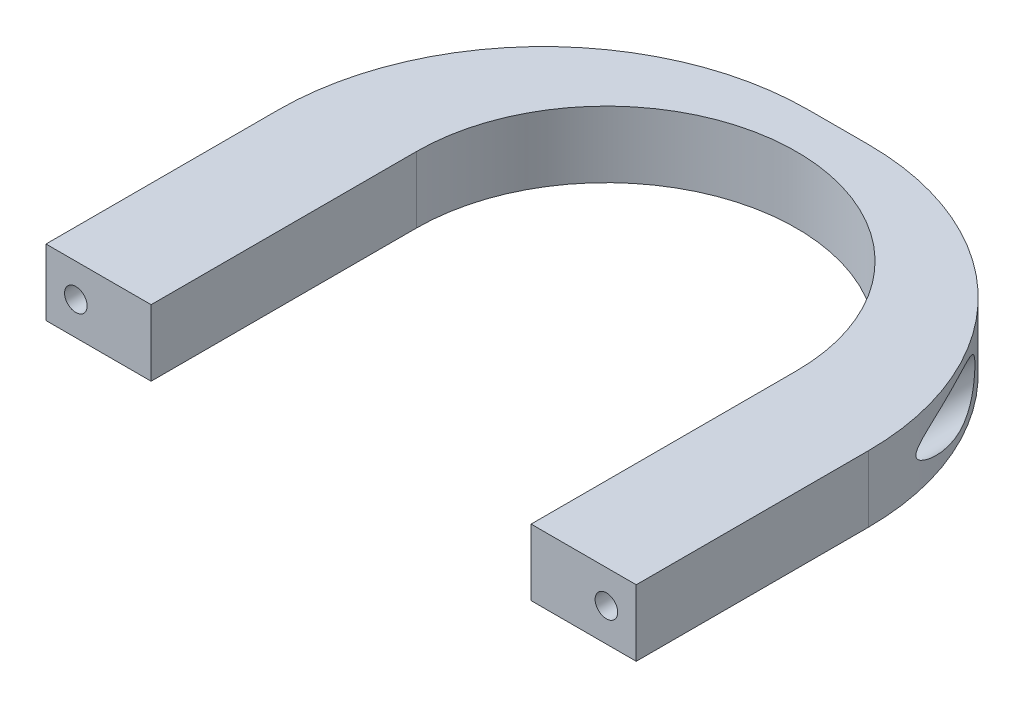
SolidWorks part; units mm, degrees
ref_plane "前视基准面" through (0, 0, 0) normal (0, 0, 1) x (1, 0, 0)
ref_plane "上视基准面" through (0, 0, 0) normal (0, 1, 0) x (1, 0, 0)
ref_plane "右视基准面" through (0, 0, 0) normal (1, 0, 0) x (0, 0, -1)
sketch "草图1" plane through (0, 0, 0) normal (0, 1, 0) x (1, 0, 0)
  line L0 (28.65, -40) -> (44.5, -40)
  line L1 (-44.5, 35) -> (44.5, 35)
  line L2 (-44.5, 35) -> (-44.5, -40)
  line L3 (-44.5, -40) -> (-28.65, -40)
  line L4 (44.5, 35) -> (44.5, -40)
  line L6 (-28.65, 0) -> (-28.65, -40)
  line L8 (28.65, 0) -> (28.65, -40)
  arc A0 (28.65, 0) -> (-28.65, 0) centre (0, 0) ccw
  dimension "D1" = 57.3
  dimension "D2" = 89
  dimension "D3" = 44.5
  dimension "D4" = 40
  dimension "D5" = 35
extrude "凸台-拉伸1" add sketch "草图1" along normal blind 10
sketch "草图2" plane through (0, 0, 40) normal (0, 0, 1) x (1, 0, 0)
  line L0 (-47.7884, 5) -> (57.4455, 5) construction
  circle A0 centre (-40, 5) radius 1.7
  circle A1 centre (40, 5) radius 1.7
  dimension "D1" = 40
  dimension "D2" = 40
  dimension "D3" = 3.4
  dimension "D4" = 3.4
extrude "切除-拉伸1" cut sketch "草图2" against normal blind 90
sketch "草图3" plane through (0, 0, -35) normal (0, 0, -1) x (-1, 0, 0)
  circle A0 centre (40, 5) radius 3.7
  circle A1 centre (-39.9988, 5) radius 3.7
  dimension "D1" = 7.4
  dimension "D2" = 7.4
extrude "切除-拉伸2" cut sketch "草图3" against normal offset from surface (43 mm away) 32 up to face at (-38.3, 5, 40)
fillet "圆角1" radius 40 2 edges at (-44.5, 5, -35) (44.5, 5, -35)
